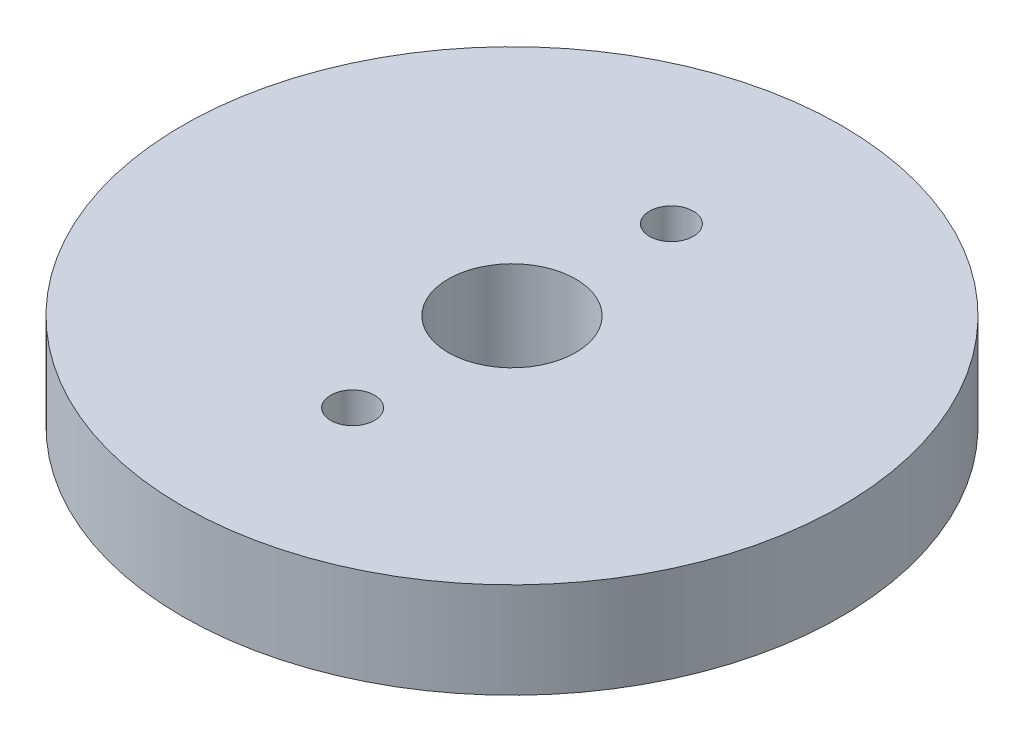
SolidWorks part; units mm, degrees
ref_plane "Front Plane" through (0, 0, 0) normal (0, 0, 1) x (1, 0, 0)
ref_plane "Top Plane" through (0, 0, 0) normal (0, 1, 0) x (1, 0, 0)
ref_plane "Right Plane" through (0, 0, 0) normal (1, 0, 0) x (0, 0, -1)
sketch "Sketch1" plane through (0, 0, 0) normal (0, 1, 0) x (1, 0, 0)
  circle A0 centre (0, 0) radius 41.35
extrude "Boss-Extrude1" add sketch "Sketch1" along normal blind 12
sketch "Sketch2" plane through (0, 12, 0) normal (0, 1, 0) x (1, 0, 0)
  circle A0 centre (0, 20) radius 2.75
  circle A1 centre (0, -20) radius 2.75
  dimension "D1" = 20
  dimension "D2" = 20
extrude "Cut-Extrude1" cut sketch "Sketch2" against normal blind 25
sketch "Sketch3" plane through (0, 12, 0) normal (0, 1, 0) x (1, 0, 0)
  circle A1 centre (0, 20) radius 5
  circle A2 centre (0, -20) radius 5
sketch "Sketch4" plane through (0, 12, 0) normal (0, 1, 0) x (1, 0, 0)
  circle A0 centre (0, 0) radius 8
extrude "Cut-Extrude2" cut sketch "Sketch4" against normal blind 25
